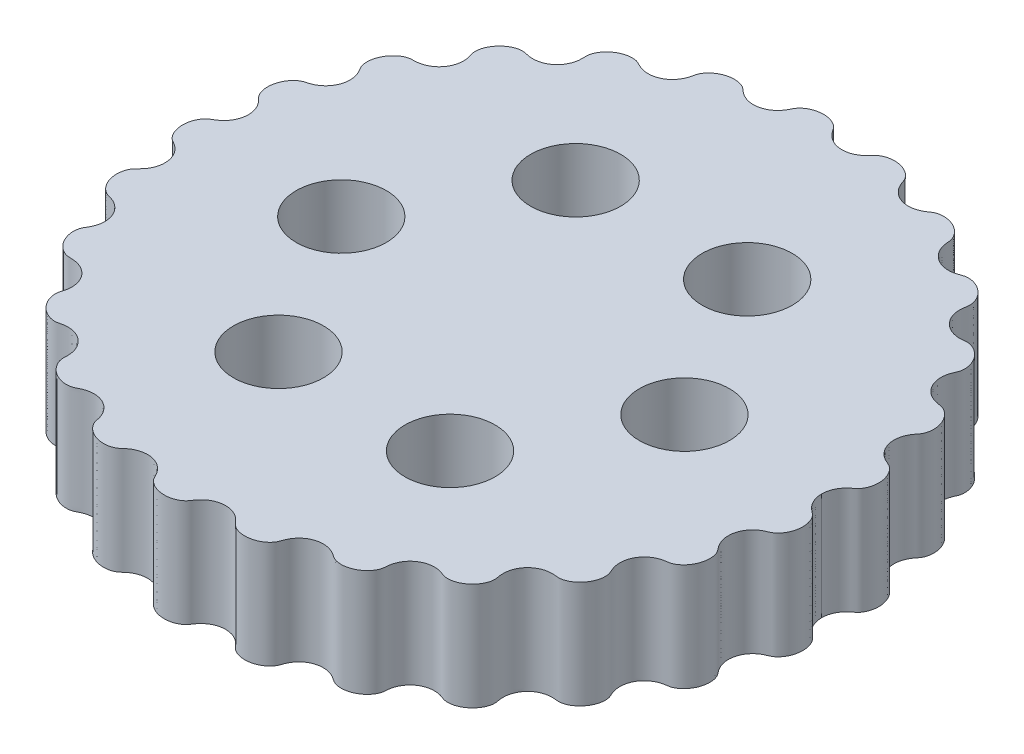
SolidWorks part; units mm, degrees
ref_plane "Front Plane" through (0, 0, 0) normal (0, 0, 1) x (1, 0, 0)
ref_plane "Top Plane" through (0, 0, 0) normal (0, 1, 0) x (1, 0, 0)
ref_plane "Right Plane" through (0, 0, 0) normal (1, 0, 0) x (0, 0, -1)
sketch "Sketch1" plane through (0, 0, 0) normal (0, 1, 0) x (1, 0, 0)
  line L0 (-15.4, 0) -> (14.4, 0) construction
  line L1 (0, 0) -> (0, -14.9128) construction
  line L2 (0, 0) -> (0, 14.9128) construction
  line L3 (-0.5, 0) -> (-0.5, -14.9128) construction
  line L4 (-0.5, 0) -> (-0.5, 14.9128) construction
  line L5 (14.4, 0) -> (15.5, 0) construction
  line L6 (0, 14.9128) -> (0, -14.9128) construction
  line L7 (5.9, 0) -> (9.1, 0) construction
  line L8 (5.9, 0) -> (7.5, 0)
  circle A0 centre (-0.5, 0) radius 16 construction
  circle A1 centre (15.5, 0) radius 1
  circle A2 centre (15.0351, -3.8291) radius 1
  circle A3 centre (13.6673, -7.4356) radius 1
  circle A4 centre (11.4762, -10.61) radius 1
  circle A5 centre (8.589, -13.1677) radius 1
  circle A6 centre (5.1737, -14.9603) radius 1
  circle A7 centre (1.4286, -15.8833) radius 1
  circle A8 centre (-2.4286, -15.8833) radius 1
  circle A9 centre (-6.1737, -14.9603) radius 1
  circle A10 centre (-9.589, -13.1677) radius 1
  circle A11 centre (-12.4762, -10.61) radius 1
  circle A12 centre (-14.6673, -7.4356) radius 1
  circle A13 centre (-16.0351, -3.8291) radius 1
  circle A14 centre (-16.5, 0) radius 1
  circle A15 centre (-16.0351, 3.8291) radius 1
  circle A16 centre (-14.6673, 7.4356) radius 1
  circle A17 centre (-12.4762, 10.61) radius 1
  circle A18 centre (-9.589, 13.1677) radius 1
  circle A19 centre (-6.1737, 14.9603) radius 1
  circle A20 centre (-2.4286, 15.8833) radius 1
  circle A21 centre (1.4286, 15.8833) radius 1
  circle A22 centre (5.1737, 14.9603) radius 1
  circle A23 centre (8.589, 13.1677) radius 1
  circle A24 centre (11.4762, 10.61) radius 1
  circle A25 centre (13.6673, 7.4356) radius 1
  circle A26 centre (15.0351, 3.8291) radius 1
  circle A27 centre (0, 0) radius 8
  circle A28 centre (8, 0) radius 2.1
  circle A29 centre (4, 6.9282) radius 2.1
  circle A30 centre (-4, 6.9282) radius 2.1
  circle A31 centre (-8, 0) radius 2.1
  circle A32 centre (-4, -6.9282) radius 2.1
  circle A33 centre (4, -6.9282) radius 2.1
  circle A34 centre (-1, 0) radius 8 construction
  circle A35 centre (3, -6.9282) radius 2.1
  circle A36 centre (-5, -6.9282) radius 2.1
  circle A37 centre (-9, 0) radius 2.1
  circle A38 centre (-5, 6.9282) radius 2.1
  circle A39 centre (3, 6.9282) radius 2.1
  circle A40 centre (7, 0) radius 2.1
  circle A41 centre (7.5, 0) radius 1.5
  circle A42 centre (3.5, -6.9282) radius 1.5
  circle A43 centre (-4.5, -6.9282) radius 1.5
  circle A44 centre (-8.5, 0) radius 1.5
  circle A45 centre (-4.5, 6.9282) radius 1.5
  circle A46 centre (3.5, 6.9282) radius 1.5
  spline S0 degree 4 number of poles 369 (14.1521, 3.1658) -> (-14.9531, 3.4358) construction
  spline S1 degree 4 number of poles 315 (14.4, 0) -> (-15.4, 0)
  spline S2 degree 4 number of poles 315 (14.4, 0) -> (-15.4, 0)
  spline S3 degree 4 number of poles 315 (-15.4, 0) -> (14.4, 0)
  spline S4 degree 4 number of poles 315 (-15.4, 0) -> (14.4, 0)
  point P80 (0, 0)
  dimension "D2" = 26
  dimension "D3" = 16
  dimension "D4" = 4.2
  dimension "D6" = 6
  dimension "D1" = 0.5
  dimension "D5" = 6
extrude "Rotor1" add sketch "Sketch1" along normal blind 5 contours S2 S1
sketch "Sketch3" plane through (0, 0, 0) normal (0, 1, 0) x (1, 0, 0)
  spline S0 degree 4 number of poles 315 (-15.4, 0) -> (14.4, 0)
  spline S1 degree 4 number of poles 315 (-15.4, 0) -> (14.4, 0)
sketch "Sketch5" plane through (0, 0, 0) normal (0, 1, 0) x (1, 0, 0)
  circle A0 centre (8, 0) radius 2.1
  circle A1 centre (4, 6.9282) radius 2.1
  circle A2 centre (-4, 6.9282) radius 2.1
  circle A3 centre (-8, 0) radius 2.1
  circle A4 centre (-4, -6.9282) radius 2.1
  circle A5 centre (4, -6.9282) radius 2.1
extrude "Cut-Extrude1" cut sketch "Sketch5" along normal through all
sketch "Sketch7" plane through (0, 0, 0) normal (0, 1, 0) x (1, 0, 0)
  circle A0 centre (3, -6.9282) radius 2.1
  circle A1 centre (-5, -6.9282) radius 2.1
  circle A2 centre (-9, 0) radius 2.1
  circle A3 centre (-5, 6.9282) radius 2.1
  circle A4 centre (3, 6.9282) radius 2.1
  circle A5 centre (7, 0) radius 2.1
sketch "Sketch8" plane through (0, 0, 0) normal (0, 1, 0) x (1, 0, 0)
  circle A0 centre (7.5, 0) radius 1.5
  circle A1 centre (3.5, -6.9282) radius 1.5
  circle A2 centre (-4.5, -6.9282) radius 1.5
  circle A3 centre (-8.5, 0) radius 1.5
  circle A4 centre (-4.5, 6.9282) radius 1.5
  circle A5 centre (3.5, 6.9282) radius 1.5
sketch "Sketch9" plane through (0, 0, 0) normal (0, 1, 0) x (1, 0, 0)
  circle A0 centre (15.5, 0) radius 1
  circle A1 centre (15.0351, -3.8291) radius 1
  circle A2 centre (13.6673, -7.4356) radius 1
  circle A3 centre (11.4762, -10.61) radius 1
  circle A4 centre (8.589, -13.1677) radius 1
  circle A5 centre (5.1737, -14.9603) radius 1
  circle A6 centre (1.4286, -15.8833) radius 1
  circle A7 centre (-2.4286, -15.8833) radius 1
  circle A8 centre (-6.1737, -14.9603) radius 1
  circle A9 centre (-9.589, -13.1677) radius 1
  circle A10 centre (-12.4762, -10.61) radius 1
  circle A11 centre (-14.6673, -7.4356) radius 1
  circle A12 centre (-16.0351, -3.8291) radius 1
  circle A13 centre (-16.5, 0) radius 1
  circle A14 centre (-16.0351, 3.8291) radius 1
  circle A15 centre (-14.6673, 7.4356) radius 1
  circle A16 centre (-12.4762, 10.61) radius 1
  circle A17 centre (-9.589, 13.1677) radius 1
  circle A18 centre (-6.1737, 14.9603) radius 1
  circle A19 centre (-2.4286, 15.8833) radius 1
  circle A20 centre (1.4286, 15.8833) radius 1
  circle A21 centre (5.1737, 14.9603) radius 1
  circle A22 centre (8.589, 13.1677) radius 1
  circle A23 centre (11.4762, 10.61) radius 1
  circle A24 centre (13.6673, 7.4356) radius 1
  circle A25 centre (15.0351, 3.8291) radius 1
